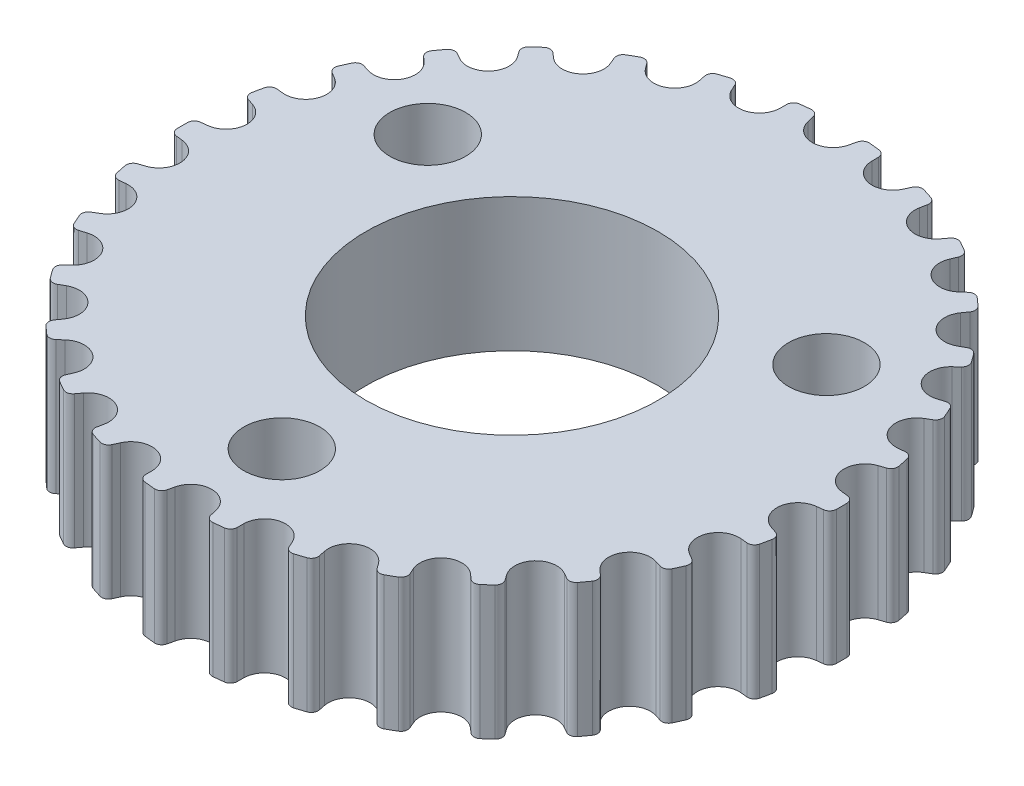
SolidWorks part; units mm, degrees
ref_plane "Front Plane" through (0, 0, 0) normal (0, 0, 1) x (1, 0, 0)
ref_plane "Top Plane" through (0, 0, 0) normal (0, 1, 0) x (1, 0, 0)
ref_plane "Right Plane" through (0, 0, 0) normal (1, 0, 0) x (0, 0, -1)
sketch "Sketch1" plane through (0, 0, 0) normal (0, 1, 0) x (1, 0, 0)
  circle A0 centre (0, 0) radius 14.3239
  dimension "D1" = 28.6479
extrude "Boss-Extrude1" add sketch "Sketch1" along normal blind 5.8
sketch "Sketch2" plane through (0, 5.8, 0) normal (0, 1, 0) x (1, 0, 0)
  line L0 (0, 0) -> (0, 14.3239) construction
  line L1 (-0.8883, 13.7564) -> (-0.95, 14.0339)
  line L2 (-2.9781, 14.0109) -> (-2.9781, 14.3239)
  line L3 (-2.9781, 14.3239) -> (2.9781, 14.3239)
  line L4 (0.8883, 13.7564) -> (0.95, 14.0339)
  line L5 (2.9781, 14.0109) -> (2.9781, 14.3239)
  circle A0 centre (0, 0) radius 14.3239 construction
  arc A1 (0.8883, 13.7564) -> (-0.8883, 13.7564) centre (0, 13.9539) cw
  arc A2 (-0.95, 14.0339) -> (-1.2694, 14.2676) centre (-1.2428, 13.9688) ccw
  arc A4 (0.95, 14.0339) -> (1.2694, 14.2676) centre (1.2428, 13.9688) cw
  arc A5 (-1.2694, 14.2676) -> (-2.9781, 14.0109) centre (0, 0) ccw
  arc A6 (1.2694, 14.2676) -> (2.9781, 14.0109) centre (0, 0) cw
  circle A8 centre (0, 0) radius 14.3239 construction
  point P11 (0, 14.3239)
  point P19 (0, 13.0439)
  dimension "D3" = 0.3
  dimension "D5" = 0.91
  dimension "D2" = 0.95
  dimension "D4" = 1.28
  dimension "D6" = 12
extrude "Cut-Extrude1" cut sketch "Sketch2" against normal through all
pattern_circular "CirPattern1" count 30 over 360 about axis through (0, 5.8, 0) along (0, -1, 0) of "Cut-Extrude1"
sketch "Sketch3" plane through (0, 0, 0) normal (0, -1, 0) x (1, 0, 0)
  circle A0 centre (0, 0) radius 6.35
  dimension "D1" = 12.7
extrude "Cut-Extrude2" cut sketch "Sketch3" against normal through all
sketch "Sketch4" plane through (0, 0, 0) normal (0, -1, 0) x (1, 0, 0)
  line L0 (0, 0) -> (0, 10) construction
  circle A0 centre (0, 10) radius 1.65
  circle A1 centre (8.6603, -5) radius 1.65
  circle A2 centre (-8.6603, -5) radius 1.65
  point P14 (0, 0)
  dimension "D1" = 3.3
  dimension "D2" = 10
  dimension "D3" = 3
extrude "Cut-Extrude3" cut sketch "Sketch4" against normal through all
equation "\"smallPulleyTeeth\"= 15"
equation "\"largePulleyTeeth\"= 30"
equation "\"eighthThick\"= 2.9mm"
equation "\"D1@Sketch1\"=3*\"largePulleyTeeth\"/pi"
equation "\"D1@Boss-Extrude1\" = \"eighthThick\" * 2"
equation "\"D6@Sketch2\"=360/\"largePulleyTeeth\""
equation "\"quarterThick\"=5.6mm"
equation "\"D1@CirPattern1\"=\"largePulleyTeeth\""
equation "\"sixteenthThick\" = 1.7mm"
equation "\"OD\" = 150mm"
equation "\"puckAngle\" = 60.5deg"
equation "\"puckDiam\" = 76.5mm"
equation "\"axlePress\" = 5.8mm"
equation "\"press\" = 0.2mm"
equation "\"wheelClear\" = 0.3mm"
equation "\"10-32clear\" = 4.5mm"
equation "\"D1@Sketch4\"=\"6-32clear\""
equation "\"6-32clear\" = 3.3mm"
equation "\"8-32clear\" = 4.0mm"
